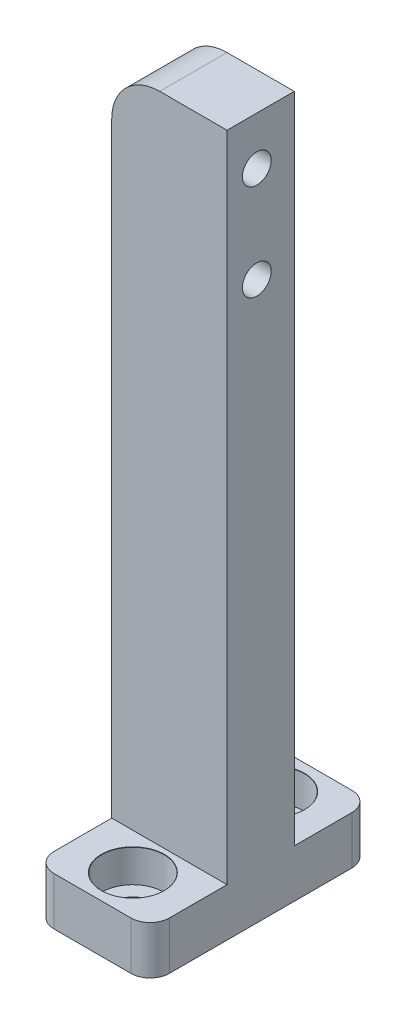
SolidWorks part; units mm, degrees
ref_plane "Front Plane" through (0, 0, 0) normal (0, 0, 1) x (1, 0, 0)
ref_plane "Top Plane" through (0, 0, 0) normal (0, 1, 0) x (1, 0, 0)
ref_plane "Right Plane" through (0, 0, 0) normal (1, 0, 0) x (0, 0, -1)
sketch "Sketch1" plane through (0, 0, 0) normal (0, 1, 0) x (1, 0, 0)
  line L1 (-6, -3.5) -> (6, -3.5)
  line L2 (-6, -3.5) -> (-6, 3.5)
  line L3 (-6, 3.5) -> (6, 3.5)
  line L4 (6, -3.5) -> (6, 3.5)
  line L5 (-6, -3.5) -> (6, 3.5) construction
  line L6 (-6, 3.5) -> (6, -3.5) construction
  point P0 (0, 0)
  dimension "D1" = 7
  dimension "D2" = 12
extrude "Boss-Extrude1" add sketch "Sketch1" along normal mid plane 73
sketch "Sketch3" plane through (0, 0, 0) normal (0, 0, 1) x (1, 0, 0)
  line L0 (-6, 36.5) -> (-6, -36.5) construction
  line L1 (-6, -31.5) -> (6, -31.5)
  line L2 (-6, -31.5) -> (-6, -36.5)
  line L3 (-6, -36.5) -> (6, -36.5)
  line L4 (6, -31.5) -> (6, -36.5)
  dimension "D1" = 5
extrude "Boss-Extrude2" add sketch "Sketch3" along normal mid plane 23
fillet "Fillet1" radius 2 4 edges at (-6, -34, -11.5) (6, -34, -11.5) (-6, -34, 11.5) (6, -34, 11.5)
hole_wizard "CBORE for M3 Hex Socket Head Cap Screw1" positions "Sketch4" profile "Sketch6" counterbore size "M3" standard "DIN" end condition through all
sketch "Sketch4" plane through (0, -31.5, 0) normal (0, 1, 0) x (1, 0, 0)
  line L0 (6, 3.5) -> (-6, 3.5) construction
  point P0 (0, 7.3)
  dimension "D1" = 3.8
sketch "Sketch6" plane through (0, -31.5, -7.3) normal (1, 0, 0) x (0, 0, 1)
  line L0 (0, 0) -> (0, 5)
  line L1 (0, 5) -> (1.7, 5)
  line L3 (1.7, 5) -> (1.7, 3.4)
  line L4 (3.25, 3.4) -> (1.7, 3.4)
  line L5 (3.25, 3.4) -> (3.25, 0.025)
  line L6 (3.25, 0.025) -> (3.275, 0)
  line L7 (3.275, 0) -> (0, 0)
  line L8 (-3.25, 0.025) -> (-3.275, 0) construction
  line L11 (0, -6.35) -> (0, 107.95) construction
  dimension "Thru Hole Dia." = 3.4
  dimension "Thru Hole Depth" = 5
  dimension "C'Bore Dia." = 6.5
  dimension "C'Bore Depth" = 3.4
  dimension "Near C'Sink Dia." = 6.55
  dimension "Near C'Sink Angle" = 90
mirror "Mirror1" about plane through (0, 0, 0) normal (0, 0, 1) of "CBORE for M3 Hex Socket Head Cap Screw1"
fillet "Fillet2" radius 5 1 edges at (-6, 36.5, 0)
sketch "Sketch7" plane through (6, 0, 0) normal (1, 0, 0) x (0, 0, -1)
  line L0 (-3.5, 36.5) -> (3.5, 36.5) construction
  line L1 (-3.5, 36.5) -> (-3.5, -31.5) construction
  circle A0 centre (-0.4, 31.5) radius 1.5
  circle A1 centre (-0.4, 21.5) radius 1.5
  point P7 (6.5932, 16.0456)
  point P8 (0, 0)
  point P9 (-1.5143, 21.6153)
  point P12 (0, 31.5)
  point P13 (0, 0)
  dimension "D1" = 3
  dimension "D2" = 5
  dimension "D3" = 10
  dimension "D4" = 3.1
extrude "Cut-Extrude1" cut sketch "Sketch7" against normal up to next
